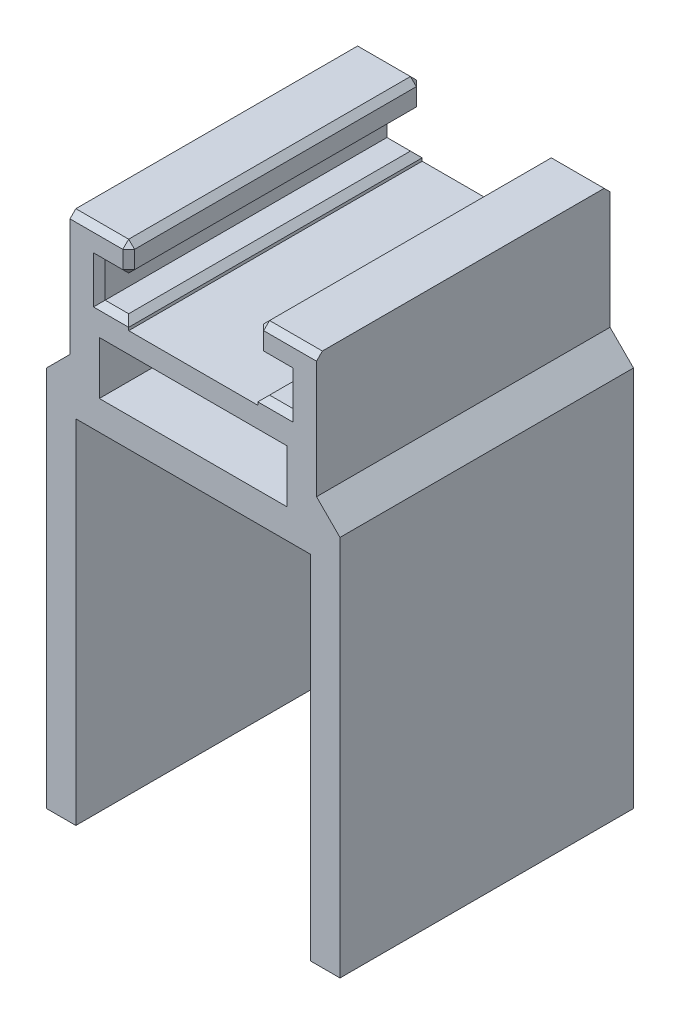
SolidWorks part; units mm, degrees
material "ABS"
ref_plane "Front Plane" through (0, 0, 0) normal (0, 0, 1) x (1, 0, 0)
ref_plane "Top Plane" through (0, 0, 0) normal (0, 1, 0) x (1, 0, 0)
ref_plane "Right Plane" through (0, 0, 0) normal (1, 0, 0) x (0, 0, -1)
sketch "Sketch1" plane through (0, 0, 0) normal (0, 0, 1) x (1, 0, 0)
  line L0 (0, 0) -> (-20, 0)
  line L1 (-20, 0) -> (-20, -60)
  line L2 (-20, -60) -> (-25, -60)
  line L3 (-25, -60) -> (-25, 5)
  line L4 (-25, 5) -> (-21, 5)
  line L5 (-21, 5) -> (-21, 30)
  line L6 (-21, 30) -> (-11, 30)
  line L7 (-11, 30) -> (-11, 25)
  line L8 (-11, 25) -> (-16, 25)
  line L9 (-16, 25) -> (-16, 19)
  line L11 (0, 17.5) -> (0, 14)
  line L12 (0, 14) -> (-16, 14)
  line L13 (-16, 14) -> (-16, 5)
  line L14 (-16, 5) -> (0, 5)
  line L15 (0, 5) -> (0, 0)
  line L16 (0, -55) -> (0, 55) construction
  line L17 (0, 17.5) -> (-11, 17.5)
  line L18 (-11, 17.5) -> (-11, 19)
  line L19 (-11, 19) -> (-16, 19)
  dimension "D1" = 20
  dimension "D2" = 5
  dimension "D3" = 16
  dimension "D4" = 5
  dimension "D5" = 5
  dimension "D6" = 60
  dimension "D7" = 5
  dimension "D8" = 3.5
  dimension "D9" = 5
  dimension "D10" = 25
  dimension "D11" = 5
  dimension "D12" = 19
extrude "Boss-Extrude1" add sketch "Sketch1" along normal blind 50
mirror "Mirror1" about plane through (0, 5, 50) normal (-1, 0, 0) of "Boss-Extrude1"
chamfer "Chamfer2" distance 1 angle 45 26 edges at (16, 22, 0) (16, 22, 50) (11, 27.5, 0) (13.5, 25, 0) (16, 30, 0) (13.5, 25, 50) (16, 30, 50) (11, 30, 25) (11, 27.5, 50) (11, 25, 25) (-13.5, 25, 0) (-11, 27.5, 0) (-16, 30, 0) (-11, 25, 25) (-11, 30, 25) (-16, 30, 50) (-11, 27.5, 50) (-13.5, 25, 50) (-16, 22, 50) (-16, 22, 0) (-13.5, 19, 0) (-11, 19, 25) (-13.5, 19, 50) (13.5, 19, 0) (11, 19, 25) (13.5, 19, 50)
chamfer "Chamfer3" distance 4 angle 45 2 edges at (21, 5, 25) (-21, 5, 25)
